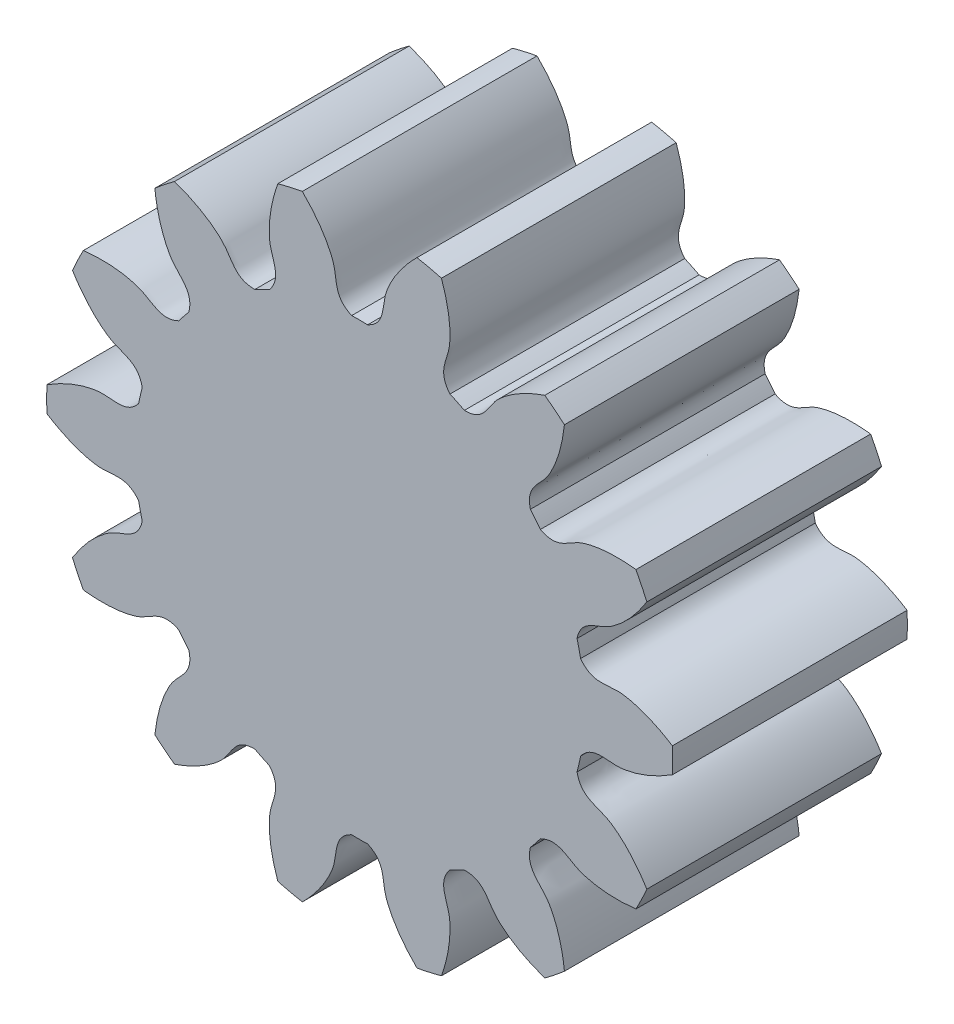
SolidWorks part; units mm, degrees
ref_plane "前视基准面" through (0, 0, 0) normal (0, 0, 1) x (1, 0, 0)
ref_plane "上视基准面" through (0, 0, 0) normal (0, 1, 0) x (1, 0, 0)
ref_plane "右视基准面" through (0, 0, 0) normal (1, 0, 0) x (0, 0, -1)
sketch "草图1" plane through (0, 0, 0) normal (0, 0, 1) x (1, 0, 0)
  circle A0 centre (0, 0) radius 4
extrude "凸台-拉伸1" add sketch "草图1" along normal blind 3
ref_axis "基准轴1" through (0, 0, -0.15) along (0, 0, 1)
sketch "草图2" plane through (0, 0, 0) normal (0, 0, 1) x (1, 0, 0)
  line L0 (0, 0) -> (0, 4) construction
  circle A0 centre (0, 0) radius 4 construction
  arc A1 (0.1022, 2.8732) -> (-0.1022, 2.8732) centre (0, 0) ccw
  arc A2 (1.612, 4.5136) -> (-1.612, 4.5136) centre (0, 0) ccw
  spline S0 degree 3 poles (0.1022, 2.8732) (0.3233, 2.974) (0.2859, 3.1585) (0.3318, 3.3257) (0.3354, 3.3377) (0.3396, 3.3509) (0.3444, 3.3652) (0.3501, 3.3806) (0.3564, 3.3972) (0.3637, 3.4149) (0.3717, 3.4336) (0.3808, 3.4533) (0.3907, 3.4741) (0.4017, 3.4958) (0.4137, 3.5185) (0.4268, 3.542) (0.4411, 3.5665) (0.4565, 3.5918) (0.4731, 3.6178) (0.491, 3.6446) (0.5101, 3.6722) (0.5306, 3.7004) (0.5525, 3.7293) (0.5757, 3.7587) (0.6003, 3.7887) (0.6264, 3.8192) (0.654, 3.8501) (0.683, 3.8815) (0.7136, 3.9132) (0.7458, 3.9452) (0.7796, 3.9775) (0.8149, 4.01) (0.8519, 4.0426) (0.8905, 4.0754) (0.9309, 4.1082) (0.9728, 4.141) (1.0165, 4.1737) (1.0619, 4.2064) (1.1091, 4.2388) (1.1579, 4.2711) (1.2086, 4.303) (1.2609, 4.3346) (1.3151, 4.3659) (1.371, 4.3966) (1.4286, 4.4269) (1.5087, 4.4669) (1.5702, 4.4953) (1.612, 4.5136) knots 0 0 0 0 0.215624 0.220482 0.225911 0.231912 0.238484 0.245628 0.253343 0.26163 0.270488 0.279917 0.289919 0.300491 0.311635 0.323351 0.335638 0.348497 0.361927 0.375928 0.390502 0.405646 0.421362 0.43765 0.454509 0.471939 0.489942 0.508515 0.52766 0.547377 0.567665 0.588524 0.609955 0.631958 0.654532 0.677677 0.701394 0.725683 0.750543 0.775974 0.801977 0.828552 0.855698 0.883415 0.911704 0.940565 1 1 1 1
  spline S1 degree 3 poles (-0.1022, 2.8732) (-0.3233, 2.974) (-0.2859, 3.1585) (-0.3318, 3.3257) (-0.3354, 3.3377) (-0.3396, 3.3509) (-0.3444, 3.3652) (-0.3501, 3.3806) (-0.3564, 3.3972) (-0.3637, 3.4149) (-0.3717, 3.4336) (-0.3808, 3.4533) (-0.3907, 3.4741) (-0.4017, 3.4958) (-0.4137, 3.5185) (-0.4268, 3.542) (-0.4411, 3.5665) (-0.4565, 3.5918) (-0.4731, 3.6178) (-0.491, 3.6446) (-0.5101, 3.6722) (-0.5306, 3.7004) (-0.5525, 3.7293) (-0.5757, 3.7587) (-0.6003, 3.7887) (-0.6264, 3.8192) (-0.654, 3.8501) (-0.683, 3.8815) (-0.7136, 3.9132) (-0.7458, 3.9452) (-0.7796, 3.9775) (-0.8149, 4.01) (-0.8519, 4.0426) (-0.8905, 4.0754) (-0.9309, 4.1082) (-0.9728, 4.141) (-1.0165, 4.1737) (-1.0619, 4.2064) (-1.1091, 4.2388) (-1.1579, 4.2711) (-1.2086, 4.303) (-1.2609, 4.3346) (-1.3151, 4.3659) (-1.371, 4.3966) (-1.4286, 4.4269) (-1.5087, 4.4669) (-1.5702, 4.4953) (-1.612, 4.5136) knots 0 0 0 0 0.215624 0.220482 0.225911 0.231912 0.238484 0.245628 0.253343 0.26163 0.270488 0.279917 0.289919 0.300491 0.311635 0.323351 0.335638 0.348497 0.361927 0.375928 0.390502 0.405646 0.421362 0.43765 0.454509 0.471939 0.489942 0.508515 0.52766 0.547377 0.567665 0.588524 0.609955 0.631958 0.654532 0.677677 0.701394 0.725683 0.750543 0.775974 0.801977 0.828552 0.855698 0.883415 0.911704 0.940565 1 1 1 1
extrude "切除-拉伸1" cut sketch "草图2" along normal through all
pattern_circular "阵列(圆周)1" count 14 every 25.714 about axis through (0, 0, -0.15) along (0, 0, 1) of "切除-拉伸1"
sketch "草图3" plane through (0, 0, 0) normal (0, 0, 1) x (1, 0, 0)
  circle A0 centre (0, 0) radius 3.5 construction
  dimension "Dn" = 7
